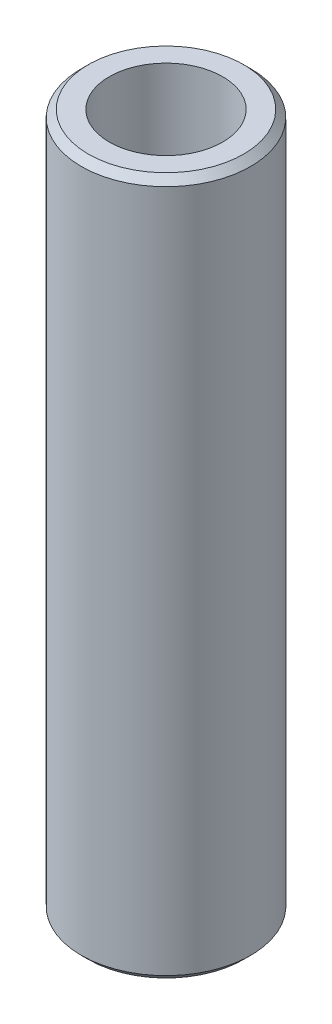
SolidWorks part; units mm, degrees
ref_plane "Front Plane" through (0, 0, 0) normal (0, 0, 1) x (1, 0, 0)
ref_plane "Top Plane" through (0, 0, 0) normal (0, 1, 0) x (1, 0, 0)
ref_plane "Right Plane" through (0, 0, 0) normal (1, 0, 0) x (0, 0, -1)
sketch "Sketch1" plane through (0, 0, 0) normal (0, 1, 0) x (1, 0, 0)
  circle A0 centre (0, 0) radius 52.5
  dimension "SHAFT_OD" = 105
extrude "Boss-Extrude1" add sketch "Sketch1" along normal blind 432.1974
sketch "Sketch2" plane through (0, 0, 0) normal (0, 1, 0) x (1, 0, 0)
  circle A0 centre (0, 0) radius 35.1374
  dimension "BORE_D" = 70.2747
extrude "Cut-Extrude1" cut sketch "Sketch2" along normal through all
chamfer "Chamfer1" distance 4.4003 angle 45 2 edges at (0, 432.1974, 52.5) (0, 0, 52.5)
